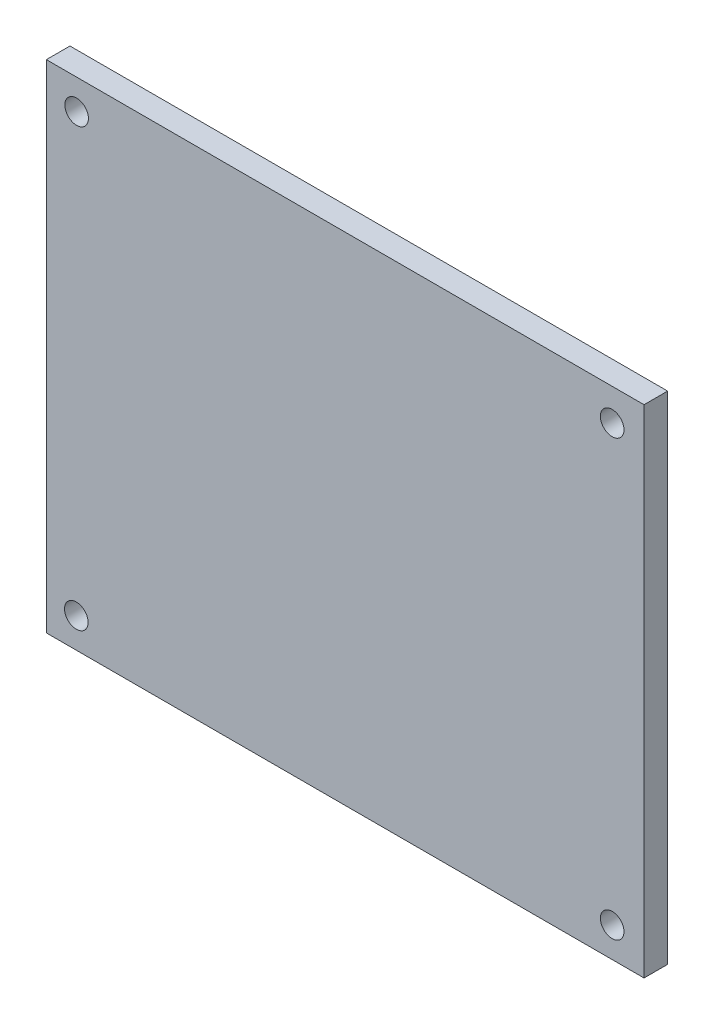
SolidWorks part; units mm, degrees
ref_plane "Plan de face" through (0, 0, 0) normal (0, 0, 1) x (1, 0, 0)
ref_plane "Plan de dessus" through (0, 0, 0) normal (0, 1, 0) x (1, 0, 0)
ref_plane "Plan de droite" through (0, 0, 0) normal (1, 0, 0) x (0, 0, -1)
sketch "Esquisse1" plane through (0, 0, 0) normal (0, 0, 1) x (1, 0, 0)
  line L1 (0, 0) -> (81.026, 0)
  line L2 (0, 0) -> (0, 67.31)
  line L3 (0, 67.31) -> (81.026, 67.31)
  line L4 (81.026, 0) -> (81.026, 67.31)
  dimension "D1" = 67.31
  dimension "D2" = 81.026
extrude "Boss.-Extru.1" add sketch "Esquisse1" along normal blind 3.2
sketch "Esquisse2" plane through (0, 0, 3.2) normal (0, 0, 1) x (1, 0, 0)
  line L0 (0, 67.31) -> (0, 0) construction
  line L2 (0, 0) -> (81.026, 0) construction
  line L4 (81.026, 67.31) -> (0, 67.31) construction
  line L5 (81.026, 0) -> (81.026, 67.31) construction
  circle A0 centre (4.064, 4.064) radius 1.6
  circle A1 centre (4.1021, 63.246) radius 1.6
  circle A2 centre (76.708, 62.992) radius 1.6
  circle A3 centre (76.708, 4.064) radius 1.6
  dimension "D3" = 3.2
  dimension "D6" = 3.2
  dimension "D9" = 3.2
  dimension "D10" = 3.2
  dimension "D1" = 4.064
  dimension "D2" = 4.064
  dimension "D4" = 4.1021
  dimension "D5" = 4.064
  dimension "D7" = 4.318
  dimension "D8" = 4.318
  dimension "D11" = 4.064
  dimension "D12" = 4.318
extrude "Enlèv. mat.-Extru.1" cut sketch "Esquisse2" against normal up to surface (3.2 mm away) up to face at (40.513, 33.655, 0)
sketch "Esquisse3" plane through (0, 0, 3.2) normal (0, 0, 1) x (1, 0, 0)
  text T0 "<b>Interface with sensors</b>"
